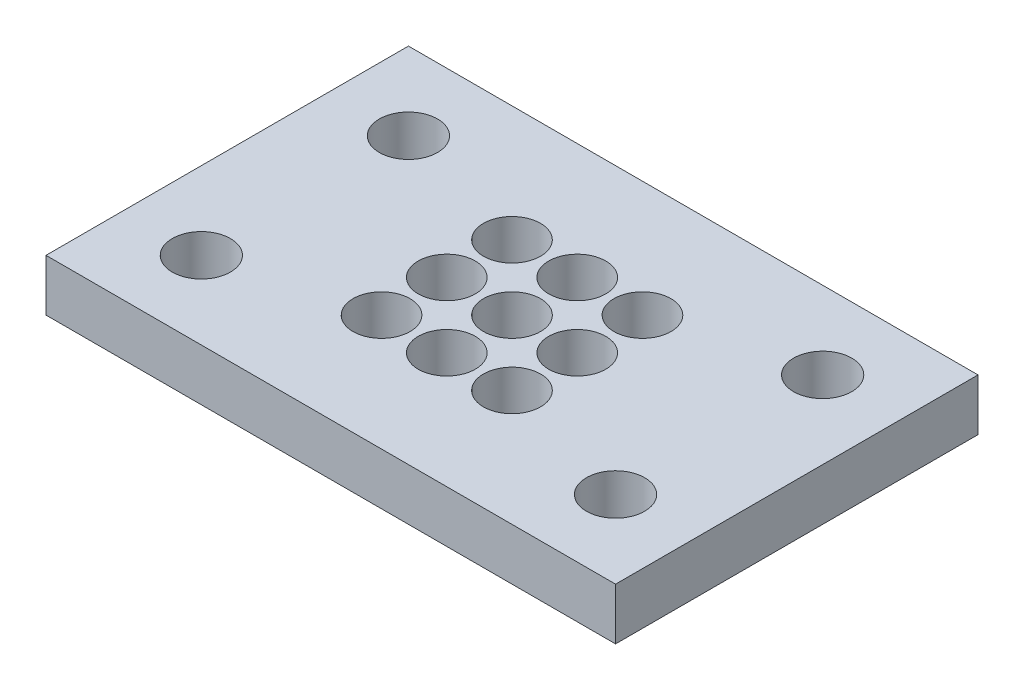
SolidWorks part; units mm, degrees
ref_plane "Front Plane" through (0, 0, 0) normal (0, 0, 1) x (1, 0, 0)
ref_plane "Top Plane" through (0, 0, 0) normal (0, 1, 0) x (1, 0, 0)
ref_plane "Right Plane" through (0, 0, 0) normal (1, 0, 0) x (0, 0, -1)
sketch "Sketch1" plane through (0, 0, 0) normal (0, 1, 0) x (1, 0, 0)
  line L0 (9.525, 34.925) -> (0, 34.925) construction
  line L1 (0, 0) -> (69.85, 0)
  line L2 (0, 0) -> (0, 44.45)
  line L3 (0, 44.45) -> (69.85, 44.45)
  line L4 (69.85, 0) -> (69.85, 44.45)
  line L5 (9.525, 34.925) -> (60.325, 34.925) construction
  line L6 (9.525, 34.925) -> (9.525, 9.525) construction
  line L7 (9.525, 9.525) -> (60.325, 9.525) construction
  line L8 (60.325, 34.925) -> (60.325, 9.525) construction
  line L9 (9.525, 34.925) -> (9.525, 44.45) construction
  circle A0 centre (9.525, 34.925) radius 3.5687
  circle A1 centre (60.325, 34.925) radius 3.5687
  circle A2 centre (9.525, 9.525) radius 3.5687
  circle A3 centre (60.325, 9.525) radius 3.5687
  circle A4 centre (34.925, 22.225) radius 3.5
  circle A5 centre (42.925, 22.225) radius 3.5
  circle A6 centre (42.925, 30.225) radius 3.5
  circle A7 centre (34.925, 30.225) radius 3.5
  circle A8 centre (26.925, 22.225) radius 3.5
  circle A9 centre (26.925, 30.225) radius 3.5
  circle A10 centre (34.925, 30.225) radius 3.5
  circle A11 centre (42.925, 22.225) radius 3.5
  circle A12 centre (42.925, 14.225) radius 3.5
  circle A13 centre (34.925, 14.225) radius 3.5
  circle A14 centre (26.925, 22.225) radius 3.5
  circle A15 centre (26.925, 14.225) radius 3.5
  circle A16 centre (34.925, 14.225) radius 3.5
  point P13 (34.925, 34.925)
  point P14 (34.925, 44.45)
  point P20 (69.85, 22.225)
  dimension "D5" = 7.1374
  dimension "D6" = 7
  dimension "D1" = 69.85
  dimension "D2" = 44.45
  dimension "D3" = 50.8
  dimension "D4" = 25.4
  dimension "D7" = 2
  dimension "D8" = 2
  dimension "D9" = 2
  dimension "D10" = 2
  dimension "D11" = 2
  dimension "D12" = 2
  dimension "D13" = 2
  dimension "D14" = 2
extrude "Boss-Extrude1" add sketch "Sketch1" along normal blind 6.35 contours L1 L4 L3 L2 A15 A13 A12 A9 A8 A7 A6 A5 A4 A3 A2 A1 A0 region at (0.8279, 0, -22.225)
